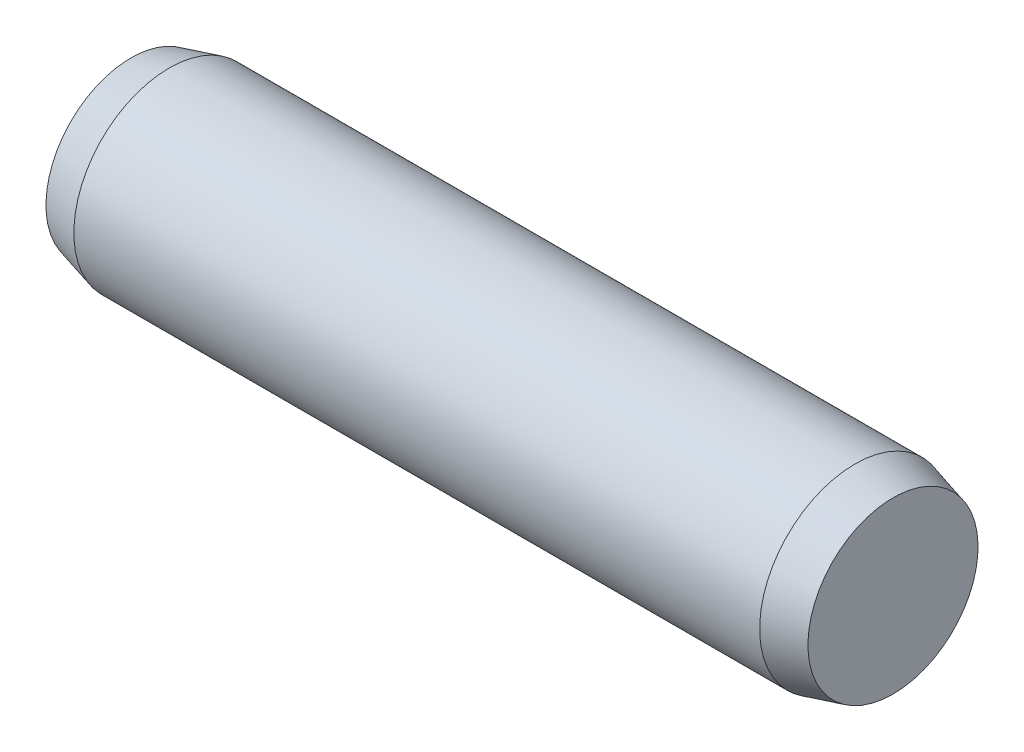
SolidWorks part; units mm, degrees
ref_plane "Front" through (0, 0, 0) normal (0, 0, 1) x (1, 0, 0)
ref_plane "Top" through (0, 0, 0) normal (0, 1, 0) x (1, 0, 0)
ref_plane "Right" through (0, 0, 0) normal (1, 0, 0) x (0, 0, -1)
sketch "Support-Front" plane through (0, 0, 0) normal (0, 0, 1) x (1, 0, 0)
  line L0 (0.6, 0) -> (6, 0) construction
  line L1 (0, 0.6696) -> (0.3, 0.75)
  line L2 (0, -0.6696) -> (0.3, -0.75)
  line L3 (0.3, 0.75) -> (5.7, 0.75)
  line L4 (0.3, -0.75) -> (5.7, -0.75)
  line L5 (0.3, 0.75) -> (0.3, -0.75) construction
  line L6 (6, -0.75) -> (6, 0.75) construction
  line L7 (6, 0.75) -> (5.7, 0.75) construction
  line L8 (6, -0.75) -> (5.7, -0.75) construction
  line L9 (5.7, 0.75) -> (5.7, -0.75) construction
  line L10 (0.6, 0) -> (0.3, 0) construction
  line L11 (0.3, 0) -> (0, 0) construction
  line L12 (0.3, 0) -> (0, 0.6696) construction
  line L13 (0, 0.6696) -> (0, -0.6696)
  line L14 (5.7, 0.75) -> (6, 0.6696)
  line L15 (6, 0.6696) -> (6, -0.6696)
  line L16 (5.7, -0.75) -> (6, -0.6696)
  line L17 (6, 0.5768) -> (5.9, 0.5768) construction
  line L18 (5.9, 0.5768) -> (5.8, 0.5768) construction
  line L19 (5.8, 0.5768) -> (5.7, 0.5768) construction
  line L20 (5.9, 0.5768) -> (5.9, 0) construction
  line L21 (5.7, 0.75) -> (6, 0.5768) construction
  arc A2 (6, 0.5768) -> (6, -0.5768) centre (7.6135, 0) ccw
  dimension "D1" = 15
  dimension "D2" = 15
  dimension "D3" = 30
  dimension "Diam" = 1.5
  dimension "Length" = 6
  dimension "Length-Chamfer-Front" = 0.3
  dimension "Length-Chamfer-Back" = 0.3
sketch "Sketch2" plane through (0, 0, 0) normal (0, 0, 1) x (1, 0, 0)
  line L9 (0.6, 0) -> (6, 0) construction
  line L12 (6, 0.6696) -> (6, -0.6696) construction
  line L14 (5.7, 0.75) -> (6, 0.6696) construction
  line L15 (0.3, 0.75) -> (5.7, 0.75) construction
  line L16 (0, 0.6696) -> (0.3, 0.75) construction
  line L17 (0, 0.6696) -> (0, -0.6696) construction
  line L18 (0, 0) -> (6, 0) construction
  line L19 (6, 0.6696) -> (6, 0)
  line L20 (5.7, 0.75) -> (6, 0.6696)
  line L21 (0.3, 0.75) -> (5.7, 0.75)
  line L22 (0, 0.6696) -> (0.3, 0.75)
  line L23 (0, 0.6696) -> (0, 0)
  line L24 (6, 0) -> (0, 0)
revolve "Body" add sketch "Sketch2" angle 360 about L18
sketch "Sketch3" plane through (0, 0, 0) normal (0, 0, 1) x (1, 0, 0)
  line L0 (0.6, 0) -> (6, 0) construction
  line L1 (6, 0.6696) -> (6, -0.6696) construction
  line L2 (5.9, 0) -> (6, 0) construction
  line L3 (6, 0.5768) -> (6, 0)
  line L4 (6, 0) -> (5.9, 0)
  arc A0 (6, 0.5768) -> (6, -0.5768) centre (7.6135, 0) ccw construction
  arc A1 (6, 0.5768) -> (5.9, 0) centre (7.6135, 0) ccw
revolve "Cut-Body" [suppressed] cut sketch "Sketch3" angle 360 about L2
equation "\"Length-Chamfer-Back@Support-Front\" = \"Length-Chamfer-Front@Support-Front\""
